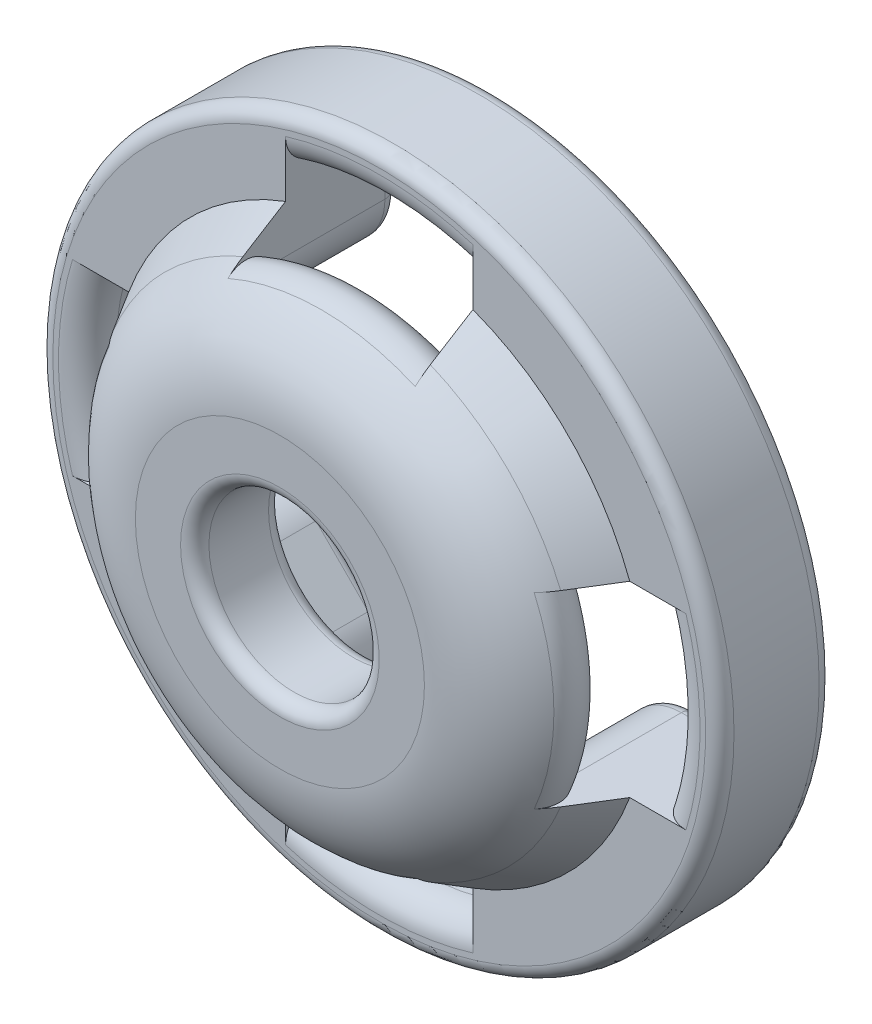
SolidWorks part; units mm, degrees
ref_plane "Front Plane" through (0, 0, 0) normal (0, 0, 1) x (1, 0, 0)
ref_plane "Top Plane" through (0, 0, 0) normal (0, 1, 0) x (1, 0, 0)
ref_plane "Right Plane" through (0, 0, 0) normal (1, 0, 0) x (0, 0, -1)
sketch "Sketch3" plane through (0, 0, 0) normal (1, 0, 0) x (0, 0, -1)
  line L0 (-3.75, 0) -> (0, 0)
  line L1 (-3.75, 0) -> (-3.75, 2.5463)
  line L2 (-2, 5) -> (-3.75, 3.9896) construction
  line L4 (-2, 0) -> (-2, 6) construction
  line L5 (0, 0) -> (0, 6)
  line L6 (-2, 4.7113) -> (-2, 6)
  line L7 (0, 6) -> (-2, 6)
  line L8 (-2.75, 4.2783) -> (-2, 4.7113)
  arc A0 (-2.75, 4.2783) -> (-3.75, 2.5463) centre (-1.75, 2.5463) ccw
  dimension "D7" = 2
  dimension "D1" = 6
  dimension "D2" = 30
  dimension "D3" = 1.75
  dimension "D4" = 2
  dimension "D5" = 5
  dimension "D6" = 0.25
revolve "Revolve1" add sketch "Sketch3" angle 360 about L0
sketch "Sketch4" plane through (0, 0, 0) normal (0, 0, -1) x (-1, 0, 0)
  line L0 (0, 5) -> (0, 0) construction
  line L1 (0, 0) -> (-5, 0) construction
  line L2 (-1.5, 4.7697) -> (-1.5, 3.0962) construction
  line L3 (-1.5, 3.0962) -> (-3.0962, 1.5) construction
  line L4 (-3.0962, 1.5) -> (-4.7697, 1.5) construction
  line L5 (-1.5, 4.7697) -> (0, 4.7697) construction
  line L6 (-4.7697, 0) -> (-4.7697, 1.5) construction
  line L7 (1.5, 3.0962) -> (1.5, 4.7697) construction
  line L8 (3.0962, 1.5) -> (1.5, 3.0962) construction
  line L9 (4.7697, 1.5) -> (3.0962, 1.5) construction
  line L10 (3.0962, -1.5) -> (4.7697, -1.5) construction
  line L11 (1.5, -3.0962) -> (3.0962, -1.5) construction
  line L12 (1.5, -4.7697) -> (1.5, -3.0962) construction
  line L13 (-1.5, -3.0962) -> (-1.5, -4.7697) construction
  line L14 (-3.0962, -1.5) -> (-1.5, -3.0962) construction
  line L15 (-4.7697, -1.5) -> (-3.0962, -1.5) construction
  line L16 (3.1583, 1.65) -> (1.65, 3.1583)
  line L17 (1.65, 3.1583) -> (1.65, 4.8785)
  line L18 (-1.65, 4.8785) -> (-1.65, 3.1583)
  line L19 (-1.65, 3.1583) -> (-3.1583, 1.65)
  line L20 (-3.1583, 1.65) -> (-4.8785, 1.65)
  line L21 (-4.8785, -1.65) -> (-3.1583, -1.65)
  line L22 (-3.1583, -1.65) -> (-1.65, -3.1583)
  line L23 (-1.65, -3.1583) -> (-1.65, -4.8785)
  line L24 (1.65, -4.8785) -> (1.65, -3.1583)
  line L25 (1.65, -3.1583) -> (3.1583, -1.65)
  line L26 (3.1583, -1.65) -> (4.8785, -1.65)
  line L27 (4.8785, 1.65) -> (3.1583, 1.65)
  arc A0 (0, 5) -> (-1.5, 4.7697) centre (0, 0) ccw construction
  arc A1 (-4.7697, 1.5) -> (-5, 0) centre (0, 0) ccw construction
  arc A2 (1.5, 4.7697) -> (0, 5) centre (0, 0) ccw construction
  arc A3 (5, 0) -> (4.7697, 1.5) centre (0, 0) ccw construction
  arc A4 (4.7697, -1.5) -> (5, 0) centre (0, 0) ccw construction
  arc A5 (0, -5) -> (1.5, -4.7697) centre (0, 0) ccw construction
  arc A6 (-1.5, -4.7697) -> (0, -5) centre (0, 0) ccw construction
  arc A7 (-5, 0) -> (-4.7697, -1.5) centre (0, 0) ccw construction
  arc A8 (1.65, 4.8785) -> (0, 5.15) centre (0, 0) ccw
  arc A9 (0, 5.15) -> (-1.65, 4.8785) centre (0, 0) ccw
  arc A10 (-4.8785, 1.65) -> (-5.15, 0) centre (0, 0) ccw
  arc A11 (-5.15, 0) -> (-4.8785, -1.65) centre (0, 0) ccw
  arc A12 (-1.65, -4.8785) -> (0, -5.15) centre (0, 0) ccw
  arc A13 (0, -5.15) -> (1.65, -4.8785) centre (0, 0) ccw
  arc A14 (4.8785, -1.65) -> (5.15, 0) centre (0, 0) ccw
  arc A15 (5.15, 0) -> (4.8785, 1.65) centre (0, 0) ccw
  point P31 (0, 0)
  dimension "D1" = 5
  dimension "D2" = 3.25
  dimension "D3" = 1.5
  dimension "D4" = 45
  dimension "D6" = 0.15
  dimension "D5" = 4
extrude "Cut-Extrude2" cut sketch "Sketch4" against normal blind 2.2
fillet "Fillet1" radius 1 8 edges at (-1.65, -3.1583, 1.1) (-3.1583, -1.65, 1.1) (-3.1583, 1.65, 1.1) (-1.65, 3.1583, 1.1) (1.65, -3.1583, 1.1) (3.1583, -1.65, 1.1) (3.1583, 1.65, 1.1) (1.65, 3.1583, 1.1)
sketch "Sketch5" plane through (0, 0, 2.2) normal (0, 0, -1) x (-1, 0, 0)
  circle A0 centre (0, 0) radius 1.5
  dimension "D1" = 3
extrude "Cut-Extrude3" cut sketch "Sketch5" against normal blind 10
fillet "Fillet2" radius 0.5 8 edges at (5.15, 0, 2) (0, -5.15, 2) (-5.15, 0, 2) (0, 5.15, 2) (0, 4.5959, 2.2) (-4.5959, 0, 2.2) (0, -4.5959, 2.2) (4.5959, 0, 2.2)
fillet "Fillet3" radius 0.25 2 edges at (-1.5, 0, 3.75) (-1.5, 0, 2.2)
fillet "Fillet4" radius 0.25 2 edges at (6, 0, 2) (6, 0, 0)
fillet "Fillet6" radius 0.25 24 edges at (-3.1899, -1.7261, 0) (-4.2255, -1.65, 0) (-5.15, 0, 0) (-4.2255, 1.65, 0) (-3.1899, 1.7261, 0) (-2.4042, 2.4042, 0) (-1.7261, 3.1899, 0) (-1.65, 4.2255, 0) (0, 5.15, 0) (1.65, 4.2255, 0) (1.7261, 3.1899, 0) (2.4042, 2.4042, 0) (3.1899, 1.7261, 0) (4.2255, 1.65, 0) (5.15, 0, 0) (4.2255, -1.65, 0) (3.1899, -1.7261, 0) (2.4042, -2.4042, 0) (1.7261, -3.1899, 0) (1.65, -4.2255, 0) (0, -5.15, 0) (-1.65, -4.2255, 0) (-1.7261, -3.1899, 0) (-2.4042, -2.4042, 0)
